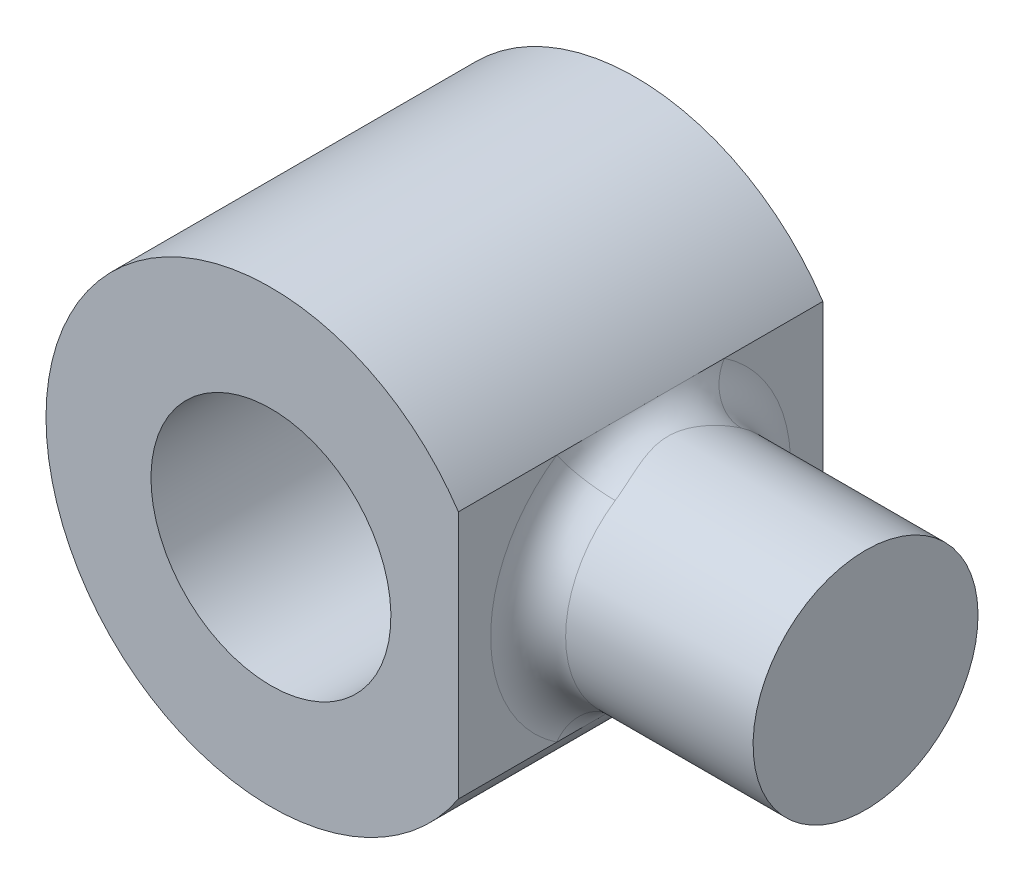
SolidWorks part; units mm, degrees
ref_plane "Front" through (0, 0, 0) normal (0, 0, 1) x (1, 0, 0)
ref_plane "Top" through (0, 0, 0) normal (0, 1, 0) x (1, 0, 0)
ref_plane "Right" through (0, 0, 0) normal (1, 0, 0) x (0, 0, -1)
sketch "Sketch1" plane through (0, 0, 0) normal (0, 0, 1) x (1, 0, 0)
  line L0 (15.0412, -1.5167) -> (15.0412, -4.8333)
  arc A0 (15.0412, -1.5167) -> (15.0412, -4.8333) centre (12.5412, -3.175) ccw
  circle A1 centre (12.5412, -3.175) radius 1.6
  dimension "D1" = 6
  dimension "D2" = 3.2
  dimension "D3" = 2.5
extrude "Boss-Extrude1" add sketch "Sketch1" against normal offset from surface 0.2 and the other way offset from surface (2.43 mm away) 0.2
sketch "Sketch2" plane through (15.0412, 0, 0) normal (1, 0, 0) x (0, 0, -1)
  line L3 (-2.43, -3.175) -> (2.43, -3.175) construction
  line L4 (-2.43, -4.8333) -> (-2.43, -1.5167) construction
  line L5 (2.43, -1.5167) -> (2.43, -4.8333) construction
  circle A0 centre (0, -3.175) radius 1.5
  point P9 (0, 0)
  dimension "D1" = 3
extrude "Boss-Extrude2" add sketch "Sketch2" along normal blind 3
fillet "Fillet1" radius 0.5 1 edges at (15.0412, -1.675, 0)
